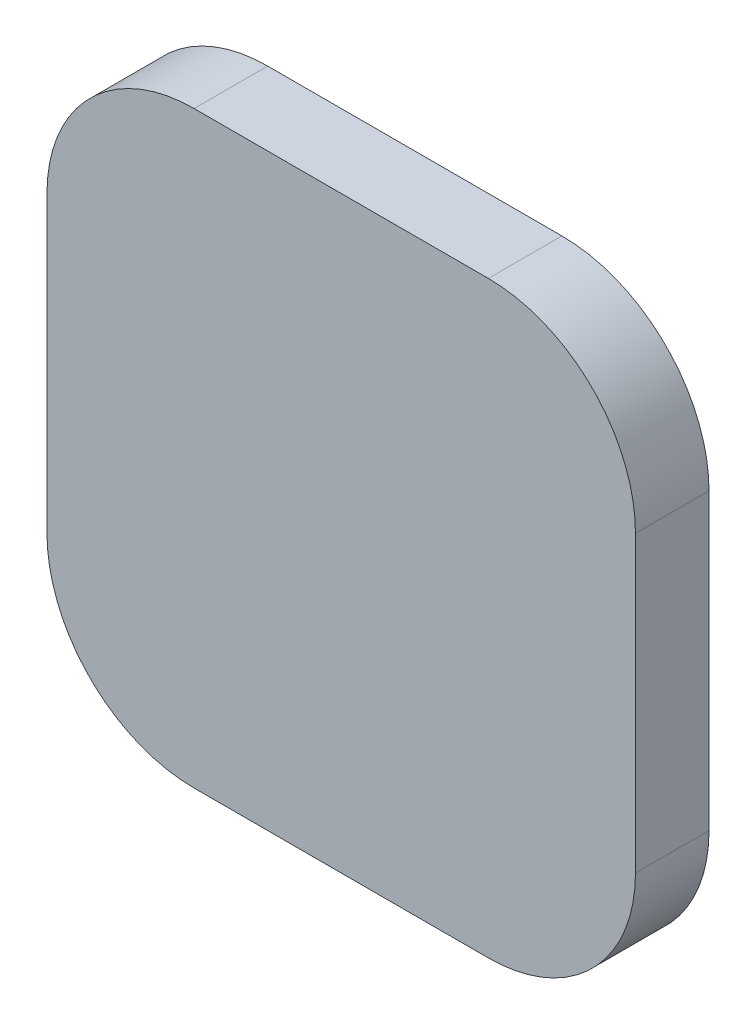
SolidWorks part; units mm, degrees
ref_plane "Front Plane" through (0, 0, 0) normal (0, 0, 1) x (1, 0, 0)
ref_plane "Top Plane" through (0, 0, 0) normal (0, 1, 0) x (1, 0, 0)
ref_plane "Right Plane" through (0, 0, 0) normal (1, 0, 0) x (0, 0, -1)
sketch "Sketch1" plane through (0, 0, 0) normal (0, 0, 1) x (1, 0, 0)
  line L1 (0, 0) -> (16, 0)
  line L2 (0, 0) -> (0, 16)
  line L3 (0, 16) -> (16, 16)
  line L4 (16, 0) -> (16, 16)
  line L5 (16, 12.25) -> (16, 9.9873)
  line L24 (16, 16) -> (-49984, 16) construction
  dimension "D1" = 16
  dimension "D2" = 16
extrude "Boss-Extrude2" add sketch "Sketch1" along normal blind 2 contours L1 L4 L3 L2 | L4 region at (8, 8, 0)
fillet "Fillet1" radius 4 4 edges at (0, 0, 1) (16, 0, 1) (16, 16, 1) (0, 16, 1)
